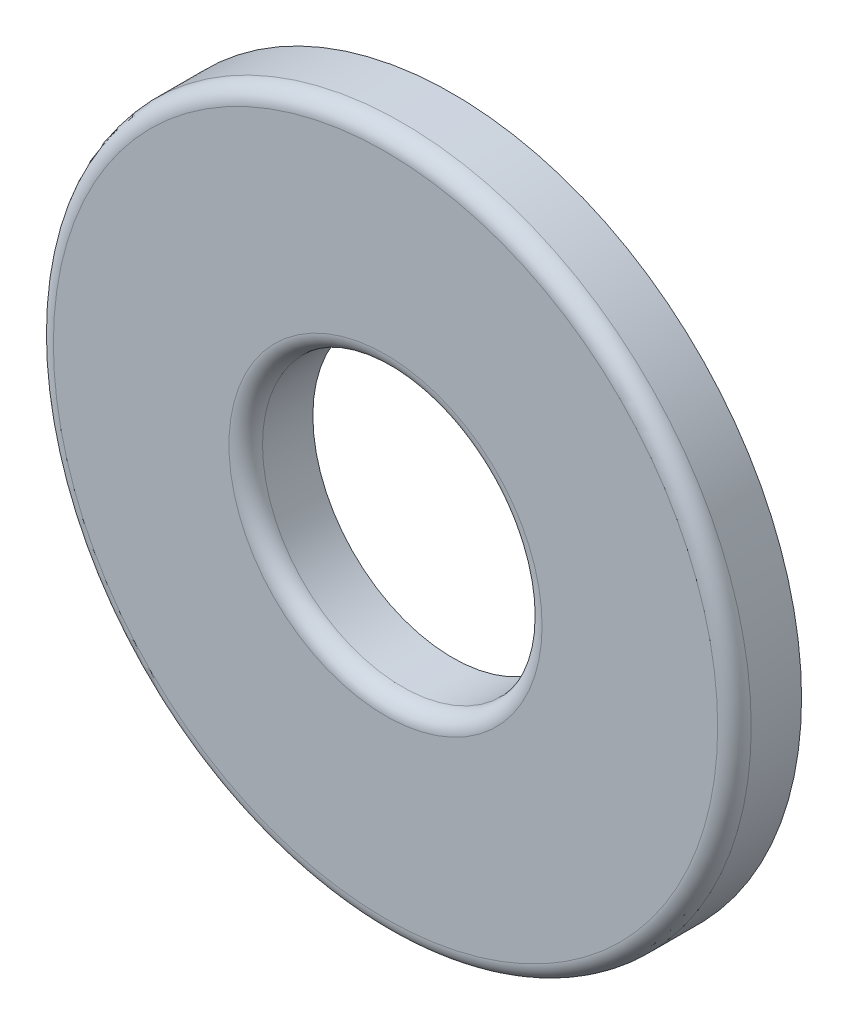
SolidWorks part; units mm, degrees
note: '?' marks a value the reader was unsure of.
other "Imported1" parameters "D1"=0.1905, "TH"=1.0287, "Thickness"=0.762
ref_plane "Front Plane" through (0, 0, 0) normal (0, 0, 1) x (1, 0, 0)
ref_plane "Top Plane" through (0, 0, 0) normal (0, 1, 0) x (1, 0, 0)
ref_plane "Right Plane" through (0, 0, 0) normal (1, 0, 0) x (0, 0, -1)
sketch "Sketch1" plane through (0, 0, 0) normal (0, 0, 1) x (1, 0, 0)
  line L0 (-3.9624, 0) -> (3.9624, 0) construction
  line L1 (-1.5875, 0) -> (1.5875, 0) construction
  circle A0 centre (0, 0) radius 1.5875 construction
  circle A1 centre (0, 0) radius 3.9624 construction
  point P8 (0, 0)
  point P9 (0, 3.9624)
  point P11 (1.5875, 0)
  dimension "ID" = 3.175
  dimension "OD" = 7.9248
sketch "Sketch2" plane through (0, 0, 0) normal (1, 0, 0) x (0, 0, -1)
  line L0 (-0.381, 3.9624) -> (0.381, 3.9624) construction
  point P2 (0, 3.9624)
sketch "Sketch3" plane through (0, 0, 0) normal (0, 0, 1) x (1, 0, 0)
  circle A0 centre (0, 0) radius 1.5875
  circle A1 centre (0, 0) radius 3.9624
extrude "Boss-Extrude1" add sketch "Sketch3" along normal up to vertex (0.381 mm away) and the other way up to vertex (0.381 mm away) up to point (0, 3.9624, 0.381) other way up to point (0, 3.9624, -0.381)
fillet "Fillet1" radius 0.1905 2 edges at (3.9624, 0, 0.381) (1.5875, 0, 0.381)
ref_axis "Center Axis 1" through (0, 0, 0.1905) along (0, 0, -1)?
equation "\"D1@Fillet1\"=\"Thickness@Sketch2\"/4"
